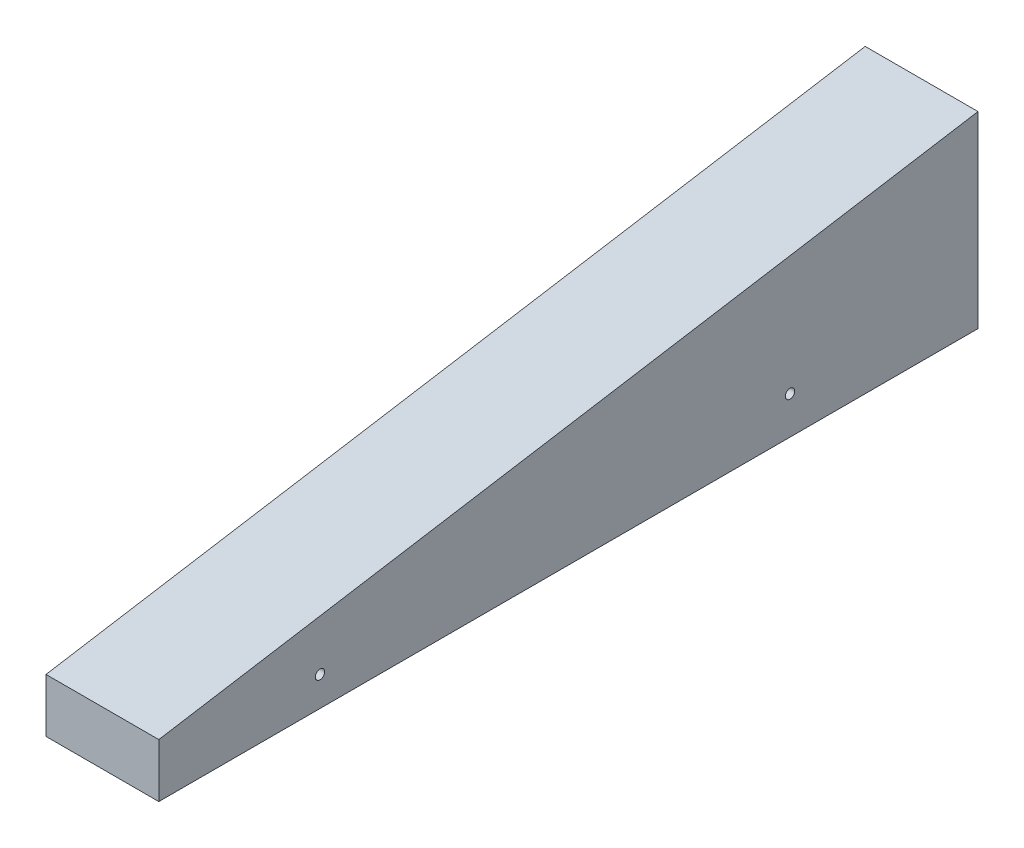
SolidWorks part; units mm, degrees
material "Balsa"
ref_plane "Front Plane" through (0, 0, 0) normal (0, 0, 1) x (1, 0, 0)
ref_plane "Top Plane" through (0, 0, 0) normal (0, 1, 0) x (1, 0, 0)
ref_plane "Right Plane" through (0, 0, 0) normal (1, 0, 0) x (0, 0, -1)
sketch "Sketch1" plane through (0, 0, 0) normal (1, 0, 0) x (0, 0, -1)
  line L1 (-152.5, 0) -> (152.5, 0)
  line L2 (-152.5, 0) -> (-152.5, 20)
  line L3 (-152.5, 20) -> (152.5, 70)
  line L4 (152.5, 0) -> (152.5, 70)
  dimension "D1" = 305
  dimension "D2" = 20
  dimension "D3" = 70
extrude "Stock Material" add sketch "Sketch1" along normal mid plane 42
sketch "Sketch2" plane through (0, 0, -152.5) normal (0, 0, -1) x (-1, 0, 0)
  line L0 (-21, 0) -> (21, 0) construction
  circle A0 centre (0, 32) radius 10
  dimension "D1" = 20
  dimension "D2" = 32
extrude "Power Plant Chamber" cut sketch "Sketch2" against normal blind 51
sketch "Axle Layout Sketch" plane through (0, 0, 0) normal (1, 0, 0) x (0, 0, -1)
  line L0 (-152.5, 0) -> (152.5, 0) construction
  line L1 (152.5, -6) -> (-152.5, -6) construction
  line L2 (152.5, 0) -> (152.5, 70) construction
  circle A0 centre (-92.5, 11) radius 1.75
  circle A1 centre (82.5, 14) radius 1.75
  circle A2 centre (-92.5, 11) radius 17 construction
  circle A3 centre (82.5, 14) radius 20 construction
  dimension "D1" = 6
  dimension "Axle Cut Diameter" = 3.5
  dimension "D2" = 175
  dimension "D3" = 70
  dimension "Rear Wheel Diameter" = 40
  dimension "Front Wheel Diameter" = 34
extrude "Axle Cutouts" cut sketch "Axle Layout Sketch" against normal through all and the other way through all
ref_axis "Rear Axle" through (21, 14, -82.5) along (-1, 0, 0)
ref_axis "Front Axle" through (21, 11, 92.5) along (-1, 0, 0)
